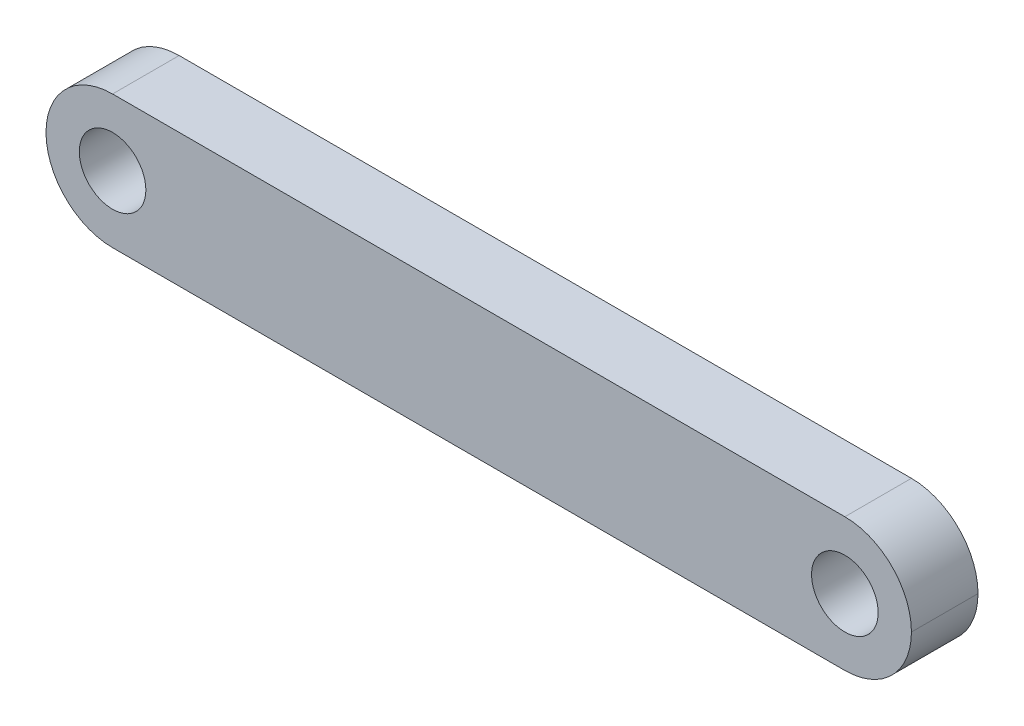
SolidWorks part; units mm, degrees
ref_plane "Front Plane" through (0, 0, 0) normal (0, 0, 1) x (1, 0, 0)
ref_plane "Top Plane" through (0, 0, 0) normal (0, 1, 0) x (1, 0, 0)
ref_plane "Right Plane" through (0, 0, 0) normal (1, 0, 0) x (0, 0, -1)
sketch "Sketch2" plane through (0, 0, 0) normal (0, 0, 1) x (1, 0, 0)
  line L1 (0, 12.7) -> (82.55, 12.7)
  line L2 (0, 12.7) -> (0, 0)
  line L3 (0, 0) -> (82.55, 0)
  line L4 (82.55, 12.7) -> (82.55, 0)
  point P4 (0, 0)
  dimension "D1" = 82.55
  dimension "D2" = 12.7
extrude "Crank Handle" add sketch "Sketch2" along normal blind 6.35
fillet "Edge 1" radius 6.35 1 edges at (82.55, 12.7, 3.175)
fillet "Edge 2" radius 6.35 1 edges at (82.55, 0, 3.175)
fillet "Edge 3" radius 6.35 1 edges at (0, 12.7, 3.175)
fillet "Edge 4" radius 6.35 1 edges at (0, 0, 3.175)
sketch "Sketch3" plane through (0, 0, 6.35) normal (0, 0, 1) x (1, 0, 0)
  circle A0 centre (6.35, 6.35) radius 3.175
  circle A1 centre (76.2, 6.35) radius 3.175
  point P6 (0, 0)
  dimension "D1" = 6.35
  dimension "D3" = 6.35
  dimension "D2" = 6.35
  dimension "D4" = 69.85
extrude "Holes" cut sketch "Sketch3" against normal through all
